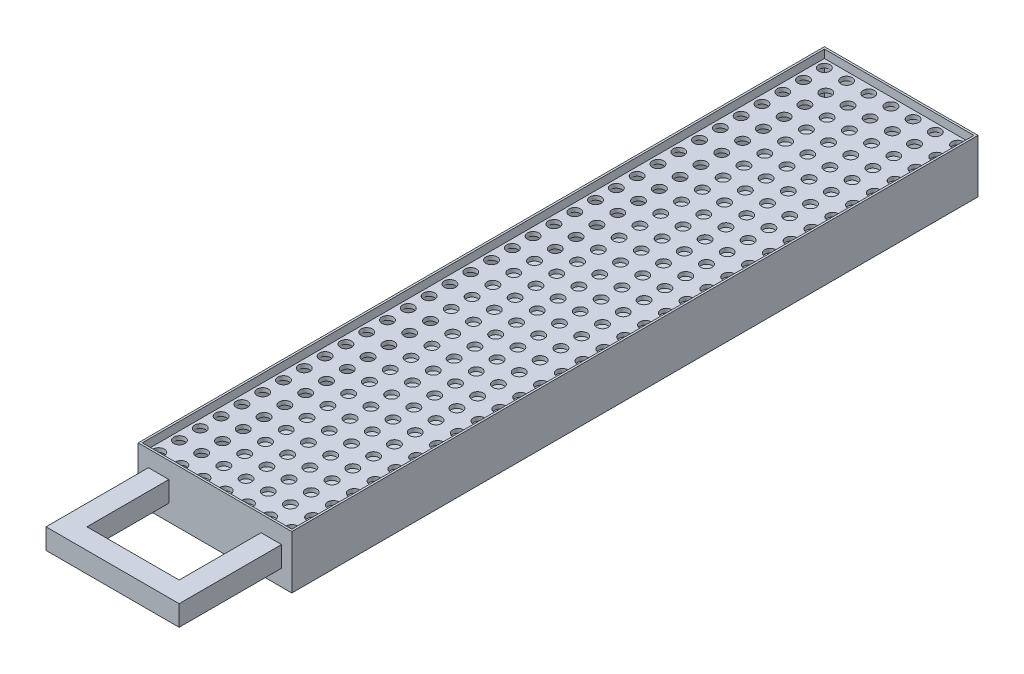
SolidWorks part; units mm, degrees
ref_plane "Alzado" through (0, 0, 0) normal (0, 0, 1) x (1, 0, 0)
ref_plane "Planta" through (0, 0, 0) normal (0, 1, 0) x (1, 0, 0)
ref_plane "Vista lateral" through (0, 0, 0) normal (1, 0, 0) x (0, 0, -1)
sketch "Croquis1" plane through (0, 0, 0) normal (0, 1, 0) x (1, 0, 0)
  line L1 (37.5, 167.5) -> (-37.5, 167.5)
  line L2 (37.5, 167.5) -> (37.5, -167.5)
  line L3 (37.5, -167.5) -> (-37.5, -167.5)
  line L4 (-37.5, 167.5) -> (-37.5, -167.5)
  line L5 (37.5, 167.5) -> (-37.5, -167.5) construction
  line L6 (37.5, -167.5) -> (-37.5, 167.5) construction
  point P0 (0, 0)
extrude "Saliente-Extruir1" add sketch "Croquis1" along normal blind 20 contours L4 L3 L2 L1
sketch "Croquis2" plane through (0, 20, 0) normal (0, 1, 0) x (1, 0, 0)
  line L0 (37.5, 167.5) -> (-37.5, 167.5) construction
  line L1 (37.5, 167.5) -> (37.5, -167.5) construction
  line L2 (-37.5, 167.5) -> (-37.5, -167.5) construction
  line L3 (37.5, -167.5) -> (-37.5, -167.5) construction
  circle A0 centre (32.5, 162.5) radius 2.75
  circle A1 centre (32.5, 152.3437) radius 2.75
  circle A2 centre (32.5, 142.1875) radius 2.75
  circle A3 centre (32.5, 132.0312) radius 2.75
  circle A4 centre (32.5, 121.875) radius 2.75
  circle A5 centre (32.5, 111.7187) radius 2.75
  circle A6 centre (32.5, 101.5625) radius 2.75
  circle A7 centre (32.5, 91.4062) radius 2.75
  circle A8 centre (32.5, 81.25) radius 2.75
  circle A9 centre (32.5, 71.0937) radius 2.75
  circle A10 centre (32.5, 60.9375) radius 2.75
  circle A11 centre (32.5, 50.7812) radius 2.75
  circle A12 centre (32.5, 40.625) radius 2.75
  circle A13 centre (32.5, 30.4687) radius 2.75
  circle A14 centre (32.5, 20.3125) radius 2.75
  circle A15 centre (32.5, 10.1562) radius 2.75
  circle A16 centre (32.5, 0) radius 2.75
  circle A17 centre (32.5, -10.1563) radius 2.75
  circle A18 centre (32.5, -20.3125) radius 2.75
  circle A19 centre (32.5, -30.4688) radius 2.75
  circle A20 centre (32.5, -40.625) radius 2.75
  circle A21 centre (32.5, -50.7813) radius 2.75
  circle A22 centre (32.5, -60.9375) radius 2.75
  circle A23 centre (32.5, -71.0938) radius 2.75
  circle A24 centre (32.5, -81.25) radius 2.75
  circle A25 centre (32.5, -91.4063) radius 2.75
  circle A26 centre (32.5, -101.5625) radius 2.75
  circle A27 centre (32.5, -111.7188) radius 2.75
  circle A28 centre (32.5, -121.875) radius 2.75
  circle A29 centre (32.5, -132.0313) radius 2.75
  circle A30 centre (32.5, -142.1875) radius 2.75
  circle A31 centre (32.5, -152.3438) radius 2.75
  circle A32 centre (32.5, -162.5) radius 2.75
  circle A33 centre (21.6667, 152.3437) radius 2.75
  circle A34 centre (21.6667, 142.1875) radius 2.75
  circle A35 centre (21.6667, 132.0312) radius 2.75
  circle A36 centre (21.6667, 121.875) radius 2.75
  circle A37 centre (21.6667, 111.7187) radius 2.75
  circle A38 centre (21.6667, 101.5625) radius 2.75
  circle A39 centre (21.6667, 91.4062) radius 2.75
  circle A40 centre (21.6667, 81.25) radius 2.75
  circle A41 centre (21.6667, 71.0937) radius 2.75
  circle A42 centre (21.6667, 60.9375) radius 2.75
  circle A43 centre (21.6667, 50.7812) radius 2.75
  circle A44 centre (21.6667, 40.625) radius 2.75
  circle A45 centre (21.6667, 30.4687) radius 2.75
  circle A46 centre (21.6667, 20.3125) radius 2.75
  circle A47 centre (21.6667, 10.1562) radius 2.75
  circle A48 centre (21.6667, 0) radius 2.75
  circle A49 centre (21.6667, -10.1563) radius 2.75
  circle A50 centre (21.6667, -20.3125) radius 2.75
  circle A51 centre (21.6667, -30.4688) radius 2.75
  circle A52 centre (21.6667, -40.625) radius 2.75
  circle A53 centre (21.6667, -50.7813) radius 2.75
  circle A54 centre (21.6667, -60.9375) radius 2.75
  circle A55 centre (21.6667, -71.0938) radius 2.75
  circle A56 centre (21.6667, -81.25) radius 2.75
  circle A57 centre (21.6667, -91.4063) radius 2.75
  circle A58 centre (21.6667, -101.5625) radius 2.75
  circle A59 centre (21.6667, -111.7188) radius 2.75
  circle A60 centre (21.6667, -121.875) radius 2.75
  circle A61 centre (21.6667, -132.0313) radius 2.75
  circle A62 centre (21.6667, -142.1875) radius 2.75
  circle A63 centre (21.6667, -152.3438) radius 2.75
  circle A64 centre (21.6667, -162.5) radius 2.75
  circle A65 centre (10.8333, 152.3437) radius 2.75
  circle A66 centre (10.8333, 142.1875) radius 2.75
  circle A67 centre (10.8333, 132.0312) radius 2.75
  circle A68 centre (10.8333, 121.875) radius 2.75
  circle A69 centre (10.8333, 111.7187) radius 2.75
  circle A70 centre (10.8333, 101.5625) radius 2.75
  circle A71 centre (10.8333, 91.4062) radius 2.75
  circle A72 centre (10.8333, 81.25) radius 2.75
  circle A73 centre (10.8333, 71.0937) radius 2.75
  circle A74 centre (10.8333, 60.9375) radius 2.75
  circle A75 centre (10.8333, 50.7812) radius 2.75
  circle A76 centre (10.8333, 40.625) radius 2.75
  circle A77 centre (10.8333, 30.4687) radius 2.75
  circle A78 centre (10.8333, 20.3125) radius 2.75
  circle A79 centre (10.8333, 10.1562) radius 2.75
  circle A80 centre (10.8333, 0) radius 2.75
  circle A81 centre (10.8333, -10.1563) radius 2.75
  circle A82 centre (10.8333, -20.3125) radius 2.75
  circle A83 centre (10.8333, -30.4688) radius 2.75
  circle A84 centre (10.8333, -40.625) radius 2.75
  circle A85 centre (10.8333, -50.7813) radius 2.75
  circle A86 centre (10.8333, -60.9375) radius 2.75
  circle A87 centre (10.8333, -71.0938) radius 2.75
  circle A88 centre (10.8333, -81.25) radius 2.75
  circle A89 centre (10.8333, -91.4063) radius 2.75
  circle A90 centre (10.8333, -101.5625) radius 2.75
  circle A91 centre (10.8333, -111.7188) radius 2.75
  circle A92 centre (10.8333, -121.875) radius 2.75
  circle A93 centre (10.8333, -132.0313) radius 2.75
  circle A94 centre (10.8333, -142.1875) radius 2.75
  circle A95 centre (10.8333, -152.3438) radius 2.75
  circle A96 centre (10.8333, -162.5) radius 2.75
  circle A97 centre (0, 152.3437) radius 2.75
  circle A98 centre (0, 142.1875) radius 2.75
  circle A99 centre (0, 132.0312) radius 2.75
  circle A100 centre (0, 121.875) radius 2.75
  circle A101 centre (0, 111.7187) radius 2.75
  circle A102 centre (0, 101.5625) radius 2.75
  circle A103 centre (0, 91.4062) radius 2.75
  circle A104 centre (0, 81.25) radius 2.75
  circle A105 centre (0, 71.0937) radius 2.75
  circle A106 centre (0, 60.9375) radius 2.75
  circle A107 centre (0, 50.7812) radius 2.75
  circle A108 centre (0, 40.625) radius 2.75
  circle A109 centre (0, 30.4687) radius 2.75
  circle A110 centre (0, 20.3125) radius 2.75
  circle A111 centre (0, 10.1562) radius 2.75
  circle A112 centre (0, 0) radius 2.75
  circle A113 centre (0, -10.1563) radius 2.75
  circle A114 centre (0, -20.3125) radius 2.75
  circle A115 centre (0, -30.4688) radius 2.75
  circle A116 centre (0, -40.625) radius 2.75
  circle A117 centre (0, -50.7813) radius 2.75
  circle A118 centre (0, -60.9375) radius 2.75
  circle A119 centre (0, -71.0938) radius 2.75
  circle A120 centre (0, -81.25) radius 2.75
  circle A121 centre (0, -91.4063) radius 2.75
  circle A122 centre (0, -101.5625) radius 2.75
  circle A123 centre (0, -111.7188) radius 2.75
  circle A124 centre (0, -121.875) radius 2.75
  circle A125 centre (0, -132.0313) radius 2.75
  circle A126 centre (0, -142.1875) radius 2.75
  circle A127 centre (0, -152.3438) radius 2.75
  circle A128 centre (0, -162.5) radius 2.75
  circle A129 centre (-10.8333, 152.3437) radius 2.75
  circle A130 centre (-10.8333, 142.1875) radius 2.75
  circle A131 centre (-10.8333, 132.0312) radius 2.75
  circle A132 centre (-10.8333, 121.875) radius 2.75
  circle A133 centre (-10.8333, 111.7187) radius 2.75
  circle A134 centre (-10.8333, 101.5625) radius 2.75
  circle A135 centre (-10.8333, 91.4062) radius 2.75
  circle A136 centre (-10.8333, 81.25) radius 2.75
  circle A137 centre (-10.8333, 71.0937) radius 2.75
  circle A138 centre (-10.8333, 60.9375) radius 2.75
  circle A139 centre (-10.8333, 50.7812) radius 2.75
  circle A140 centre (-10.8333, 40.625) radius 2.75
  circle A141 centre (-10.8333, 30.4687) radius 2.75
  circle A142 centre (-10.8333, 20.3125) radius 2.75
  circle A143 centre (-10.8333, 10.1562) radius 2.75
  circle A144 centre (-10.8333, 0) radius 2.75
  circle A145 centre (-10.8333, -10.1563) radius 2.75
  circle A146 centre (-10.8333, -20.3125) radius 2.75
  circle A147 centre (-10.8333, -30.4688) radius 2.75
  circle A148 centre (-10.8333, -40.625) radius 2.75
  circle A149 centre (-10.8333, -50.7813) radius 2.75
  circle A150 centre (-10.8333, -60.9375) radius 2.75
  circle A151 centre (-10.8333, -71.0938) radius 2.75
  circle A152 centre (-10.8333, -81.25) radius 2.75
  circle A153 centre (-10.8333, -91.4063) radius 2.75
  circle A154 centre (-10.8333, -101.5625) radius 2.75
  circle A155 centre (-10.8333, -111.7188) radius 2.75
  circle A156 centre (-10.8333, -121.875) radius 2.75
  circle A157 centre (-10.8333, -132.0313) radius 2.75
  circle A158 centre (-10.8333, -142.1875) radius 2.75
  circle A159 centre (-10.8333, -152.3438) radius 2.75
  circle A160 centre (-10.8333, -162.5) radius 2.75
  circle A161 centre (-21.6667, 152.3437) radius 2.75
  circle A162 centre (-21.6667, 142.1875) radius 2.75
  circle A163 centre (-21.6667, 132.0312) radius 2.75
  circle A164 centre (-21.6667, 121.875) radius 2.75
  circle A165 centre (-21.6667, 111.7187) radius 2.75
  circle A166 centre (-21.6667, 101.5625) radius 2.75
  circle A167 centre (-21.6667, 91.4062) radius 2.75
  circle A168 centre (-21.6667, 81.25) radius 2.75
  circle A169 centre (-21.6667, 71.0937) radius 2.75
  circle A170 centre (-21.6667, 60.9375) radius 2.75
  circle A171 centre (-21.6667, 50.7812) radius 2.75
  circle A172 centre (-21.6667, 40.625) radius 2.75
  circle A173 centre (-21.6667, 30.4687) radius 2.75
  circle A174 centre (-21.6667, 20.3125) radius 2.75
  circle A175 centre (-21.6667, 10.1562) radius 2.75
  circle A176 centre (-21.6667, 0) radius 2.75
  circle A177 centre (-21.6667, -10.1563) radius 2.75
  circle A178 centre (-21.6667, -20.3125) radius 2.75
  circle A179 centre (-21.6667, -30.4688) radius 2.75
  circle A180 centre (-21.6667, -40.625) radius 2.75
  circle A181 centre (-21.6667, -50.7813) radius 2.75
  circle A182 centre (-21.6667, -60.9375) radius 2.75
  circle A183 centre (-21.6667, -71.0938) radius 2.75
  circle A184 centre (-21.6667, -81.25) radius 2.75
  circle A185 centre (-21.6667, -91.4063) radius 2.75
  circle A186 centre (-21.6667, -101.5625) radius 2.75
  circle A187 centre (-21.6667, -111.7188) radius 2.75
  circle A188 centre (-21.6667, -121.875) radius 2.75
  circle A189 centre (-21.6667, -132.0313) radius 2.75
  circle A190 centre (-21.6667, -142.1875) radius 2.75
  circle A191 centre (-21.6667, -152.3438) radius 2.75
  circle A192 centre (-21.6667, -162.5) radius 2.75
  circle A193 centre (-32.5, 152.3437) radius 2.75
  circle A194 centre (-32.5, 142.1875) radius 2.75
  circle A195 centre (-32.5, 132.0312) radius 2.75
  circle A196 centre (-32.5, 121.875) radius 2.75
  circle A197 centre (-32.5, 111.7187) radius 2.75
  circle A198 centre (-32.5, 101.5625) radius 2.75
  circle A199 centre (-32.5, 91.4062) radius 2.75
  circle A200 centre (-32.5, 81.25) radius 2.75
  circle A201 centre (-32.5, 71.0937) radius 2.75
  circle A202 centre (-32.5, 60.9375) radius 2.75
  circle A203 centre (-32.5, 50.7812) radius 2.75
  circle A204 centre (-32.5, 40.625) radius 2.75
  circle A205 centre (-32.5, 30.4687) radius 2.75
  circle A206 centre (-32.5, 20.3125) radius 2.75
  circle A207 centre (-32.5, 10.1562) radius 2.75
  circle A208 centre (-32.5, 0) radius 2.75
  circle A209 centre (-32.5, -10.1563) radius 2.75
  circle A210 centre (-32.5, -20.3125) radius 2.75
  circle A211 centre (-32.5, -30.4688) radius 2.75
  circle A212 centre (-32.5, -40.625) radius 2.75
  circle A213 centre (-32.5, -50.7813) radius 2.75
  circle A214 centre (-32.5, -60.9375) radius 2.75
  circle A215 centre (-32.5, -71.0938) radius 2.75
  circle A216 centre (-32.5, -81.25) radius 2.75
  circle A217 centre (-32.5, -91.4063) radius 2.75
  circle A218 centre (-32.5, -101.5625) radius 2.75
  circle A219 centre (-32.5, -111.7188) radius 2.75
  circle A220 centre (-32.5, -121.875) radius 2.75
  circle A221 centre (-32.5, -132.0313) radius 2.75
  circle A222 centre (-32.5, -142.1875) radius 2.75
  circle A223 centre (-32.5, -152.3438) radius 2.75
  circle A224 centre (-32.5, -162.5) radius 2.75
  circle A225 centre (21.6667, 162.5) radius 2.75
  circle A226 centre (10.8333, 162.5) radius 2.75
  circle A227 centre (0, 162.5) radius 2.75
  circle A228 centre (-10.8333, 162.5) radius 2.75
  circle A229 centre (-21.6667, 162.5) radius 2.75
  circle A230 centre (-32.5, 162.5) radius 2.75
  dimension "D1" = 5
  dimension "D2" = 5
  dimension "D5" = 5
  dimension "D6" = 5
  dimension "D3" = 33
  dimension "D4" = 7
shell "Vaciado1" thickness 2 removed face at (0, 0, 0)
extrude "Cortar-Extruir1" cut sketch "Croquis2" against normal up to next (2 mm away)
sketch "Croquis3" plane through (35.5, 0, 0) normal (-1, 0, 0) x (0, 0, 1)
  line L0 (-165.5, 18) -> (-165.5, 0) construction
  line L5 (-23, 8) -> (22.2559, 8)
  line L6 (-23, 8) -> (-23, 3)
  line L7 (-23, 3) -> (22.2559, 3)
  line L8 (22.2559, 8) -> (22.2559, 3)
  line L9 (-23, 8) -> (22.2559, 3) construction
  line L10 (-23, 3) -> (22.2559, 8) construction
  line L25 (-165.5, 0) -> (165.5, 0) construction
  point P0 (-0.372, 5.5)
  point P5 (0, 0)
  point P14 (-165.5, 18)
  dimension "D1" = 3
  dimension "D2" = 5
  dimension "D3" = 142.5
extrude "Saliente-Extruir3" add sketch "Croquis3" along normal up to next
sketch "Croquis4" plane through (0, 0, 0) normal (0, -1, 0) x (1, 0, 0)
  line L1 (-37.5, 167.5) -> (37.5, 167.5)
  line L2 (-37.5, 167.5) -> (-37.5, -167.5)
  line L3 (-37.5, -167.5) -> (37.5, -167.5)
  line L4 (37.5, 167.5) -> (37.5, -167.5)
  line L5 (-37.5, 167.5) -> (37.5, -167.5) construction
  line L6 (-37.5, -167.5) -> (37.5, 167.5) construction
  point P4 (0, 0)
extrude "Saliente-Extruir5" add sketch "Croquis4" along normal blind 2
sketch "Croquis6" plane through (0, 20, 0) normal (0, 1, 0) x (1, 0, 0)
  line L1 (-37.5, 167.5) -> (37.5, 167.5)
  line L2 (-37.5, 167.5) -> (-37.5, -167.5)
  line L3 (-37.5, -167.5) -> (37.5, -167.5)
  line L4 (37.5, 167.5) -> (37.5, -167.5)
  line L5 (-37.5, 167.5) -> (37.5, -167.5) construction
  line L6 (-37.5, -167.5) -> (37.5, 167.5) construction
  line L11 (37.5, -167.5) -> (-37.5, -167.5) construction
  line L12 (-37.5, 167.5) -> (-37.5, -167.5) construction
  point P4 (0, 0)
extrude "Saliente-Extruir6" add sketch "Croquis6" along normal blind 4
sketch "Croquis9" plane through (0, 24, 0) normal (0, 1, 0) x (1, 0, 0)
  line L0 (-37.5, 167.5) -> (-37.5, -167.5) construction
  line L1 (-36.5, 166.5) -> (36.5, 166.5)
  line L2 (-36.5, 166.5) -> (-36.5, -166.5)
  line L3 (-36.5, -166.5) -> (36.5, -166.5)
  line L4 (36.5, 166.5) -> (36.5, -166.5)
  line L5 (-36.5, 166.5) -> (36.5, -166.5) construction
  line L6 (-36.5, -166.5) -> (36.5, 166.5) construction
  line L7 (-37.5, -167.5) -> (37.5, -167.5) construction
  line L8 (37.5, -167.5) -> (37.5, 167.5) construction
  line L9 (37.5, 167.5) -> (-37.5, 167.5) construction
  point P4 (0, 0)
  dimension "D1" = 1
  dimension "D2" = 1
  dimension "D3" = 1
  dimension "D4" = 1
extrude "Cortar-Extruir2" cut sketch "Croquis9" against normal blind 4
sketch "Croquis10" plane through (0, -2, 0) normal (0, -1, 0) x (1, 0, 0)
  line L0 (37.5, 167.5) -> (-37.5, 167.5) construction
  line L1 (-37.5, 167.5) -> (-37.5, -167.5) construction
  circle A0 centre (-29.5, 159.5) radius 5
  dimension "D1" = 10
  dimension "D2" = 8
  dimension "D3" = 8
extrude "Cortar-Extruir3" cut sketch "Croquis10" against normal up to next
sketch "Croquis11" plane through (0, 0, 167.5) normal (0, 0, 1) x (1, 0, 0)
  line L0 (-37.5, 24) -> (-37.5, -2) construction
  line L1 (-32.5, 16) -> (-22.5, 16)
  line L2 (-32.5, 16) -> (-32.5, 6)
  line L3 (-32.5, 6) -> (-22.5, 6)
  line L4 (-22.5, 16) -> (-22.5, 6)
  line L5 (-32.5, 16) -> (-22.5, 6) construction
  line L6 (-32.5, 6) -> (-22.5, 16) construction
  line L8 (-37.5, 24) -> (37.5, 24) construction
  line L10 (37.5, -2) -> (-37.5, -2) construction
  line L11 (0, 24) -> (0, -2)
  line L12 (32.5, 6) -> (22.5, 6)
  line L13 (22.5, 16) -> (22.5, 6)
  line L14 (32.5, 16) -> (22.5, 16)
  line L15 (32.5, 16) -> (32.5, 6)
  point P4 (-27.5, 11)
  dimension "D1" = 5
  dimension "D2" = 10
  dimension "D3" = 8
extrude "Saliente-Extruir7" add sketch "Croquis11" along normal blind 50 contours L15 L14 L13 L12 | L3 L4 L1 L2 region at (27.5, 11, 167.5)
sketch "Croquis12" plane through (-22.5, 0, 0) normal (1, 0, 0) x (0, 0, -1)
  line L0 (-207.5, 16) -> (-207.5, 6)
  line L1 (-217.5, 16) -> (-167.5, 16) construction
  line L2 (-217.5, 6) -> (-167.5, 6) construction
  line L3 (-217.5, 16) -> (-217.5, 6) construction
  line L8 (-167.5, 6) -> (-167.5, 16)
  line L9 (-167.5, 16) -> (-217.5, 16)
  line L10 (-217.5, 16) -> (-217.5, 6)
  line L11 (-217.5, 6) -> (-167.5, 6)
  line L13 (-207.5, 16) -> (-217.5, 16)
  line L14 (-217.5, 16) -> (-217.5, 6)
  line L15 (-217.5, 6) -> (-207.5, 6)
  dimension "D1" = 10
  dimension "D2" = 0
extrude "Saliente-Extruir8" add sketch "Croquis12" along normal up to next
